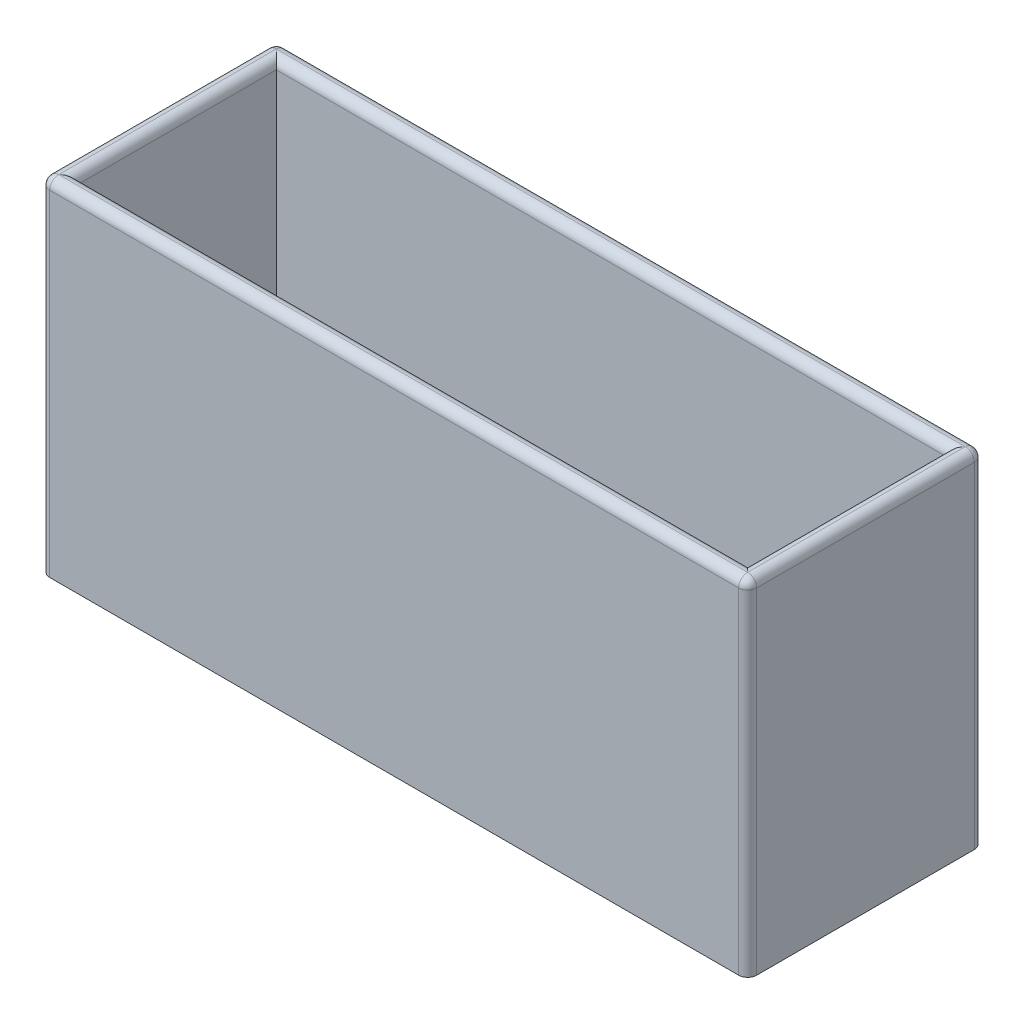
SolidWorks part; units mm, degrees
ref_plane "Front Plane" through (0, 0, 0) normal (0, 0, 1) x (1, 0, 0)
ref_plane "Top Plane" through (0, 0, 0) normal (0, 1, 0) x (1, 0, 0)
ref_plane "Right Plane" through (0, 0, 0) normal (1, 0, 0) x (0, 0, -1)
sketch "Sketch1" plane through (0, 0, 0) normal (0, 1, 0) x (1, 0, 0)
  line L1 (0, 0) -> (78, 0)
  line L2 (0, 0) -> (0, 26)
  line L3 (0, 26) -> (78, 26)
  line L4 (78, 0) -> (78, 26)
  dimension "D1" = 78
  dimension "D2" = 26
extrude "Boss-Extrude1" add sketch "Sketch1" along normal blind 38
sketch "Sketch2" plane through (0, 38, 0) normal (0, 1, 0) x (1, 0, 0)
  line L0 (0, 0) -> (78, 0) construction
  line L1 (2, 2) -> (76, 2)
  line L2 (2, 2) -> (2, 24)
  line L3 (2, 24) -> (76, 24)
  line L4 (76, 2) -> (76, 24)
  line L5 (0, 26) -> (0, 0) construction
  line L6 (78, 0) -> (78, 26) construction
  line L7 (78, 26) -> (0, 26) construction
  point P4 (39, 2)
  dimension "D1" = 2
  dimension "D2" = 2
  dimension "D3" = 2
  dimension "D4" = 2
extrude "Cut-Extrude1" cut sketch "Sketch2" against normal blind 36
sketch "Sketch4" plane through (0, 0, 0) normal (0, -1, 0) x (1, 0, 0)
  line L0 (0, 0) -> (78, 0) construction
  line L1 (78, -26) -> (0, -26) construction
  line L2 (78, 0) -> (78, -26) construction
  line L3 (0, -26) -> (0, 0) construction
  circle A0 centre (71, -7) radius 1.5
  circle A1 centre (71, -19) radius 1.5
  circle A2 centre (7, -19) radius 1.5
  circle A3 centre (7, -7) radius 1.5
  point P16 (9, -9)
  point P17 (9, -9)
  dimension "D1" = 3
  dimension "D2" = 7
  dimension "D3" = 7
  dimension "D4" = 7
  dimension "D5" = 7
  dimension "D6" = 7
  dimension "D7" = 7
  dimension "D8" = 7
  dimension "D9" = 7
extrude "Cut-Extrude3" cut sketch "Sketch4" against normal blind 2
fillet "Fillet1" radius 1 12 edges at (39, 38, -26) (78, 38, -13) (39, 38, 0) (0, 38, -13) (76, 38, -13) (39, 38, -24) (2, 38, -13) (39, 38, -2) (78, 19, 0) (78, 19, -26) (0, 19, 0) (0, 19, -26)
